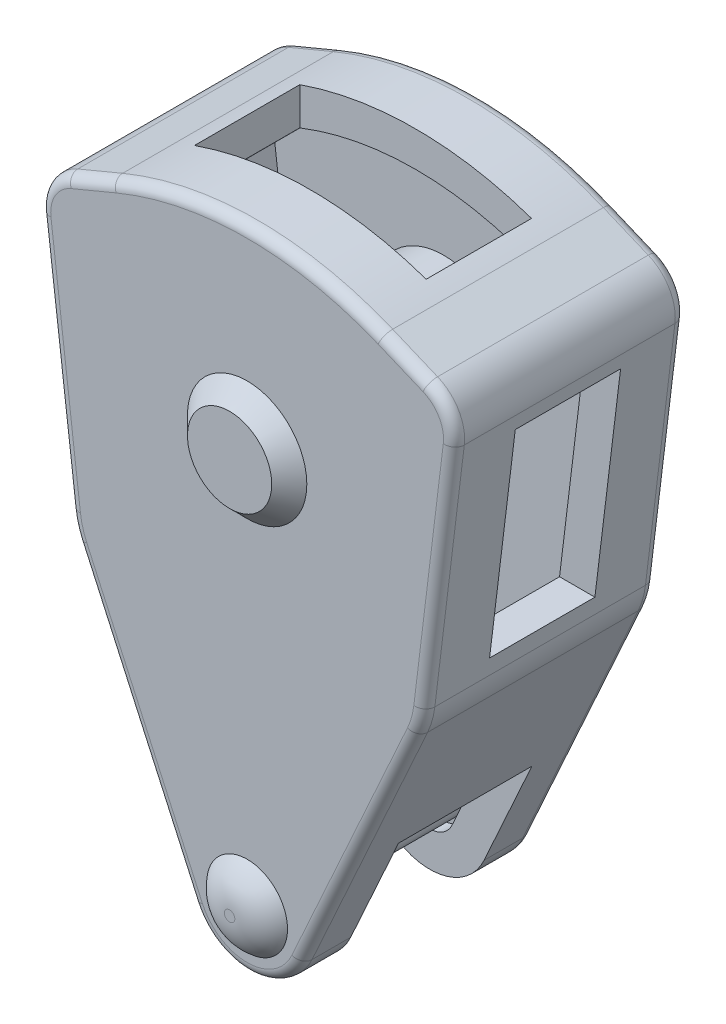
SolidWorks part; units mm, degrees
material "ABS"
ref_plane "Front Plane" through (0, 0, 0) normal (0, 0, 1) x (1, 0, 0)
ref_plane "Top Plane" through (0, 0, 0) normal (0, 1, 0) x (1, 0, 0)
ref_plane "Right Plane" through (0, 0, 0) normal (1, 0, 0) x (0, 0, -1)
sketch "Sketch1" plane through (0, 0, 0) normal (0, 0, 1) x (1, 0, 0)
  line L0 (3.9317, -1.7852) -> (12.7, 17.526)
  line L1 (12.7, 17.526) -> (15.24, 38.354)
  line L2 (15.24, 38.354) -> (0, 44.704)
  line L3 (0, 0) -> (0, 44.704) construction
  line L4 (0, 0) -> (0, -4.318) construction
  line L5 (-15.24, 38.354) -> (0, 44.704)
  line L6 (-12.7, 17.526) -> (-15.24, 38.354)
  line L7 (-3.9317, -1.7852) -> (-12.7, 17.526)
  arc A0 (-3.9317, -1.7852) -> (3.9317, -1.7852) centre (0, 0) ccw
  dimension "D1" = 8.636
  dimension "D2" = 12.7
  dimension "D3" = 15.24
  dimension "D4" = 49.022
  dimension "D5" = 21.844
  dimension "D6" = 42.672
extrude "Boss-Extrude1" add sketch "Sketch1" along normal mid plane 16.764
fillet "Fillet1" radius 25.4 1 edges at (0, 44.704, 0)
fillet "Fillet2" radius 3.175 2 edges at (15.24, 38.354, 0) (-15.24, 38.354, 0)
fillet "Fillet3" radius 6.35 2 edges at (12.7, 17.526, 0) (-12.7, 17.526, 0)
shell "Shell1" thickness 2.54
sketch "Sketch2" plane through (0, 0, 0) normal (1, 0, 0) x (0, 0, -1)
  line L0 (-8.382, -4.318) -> (8.382, -4.318) construction
  line L1 (-4.826, -4.318) -> (4.826, -4.318)
  line L2 (-4.826, -4.318) -> (-4.826, 5.842)
  line L3 (-4.826, 5.842) -> (4.826, 5.842)
  line L4 (4.826, -4.318) -> (4.826, 5.842)
  line L5 (0, 5.842) -> (0, 0) construction
  dimension "D1" = 9.652
  dimension "D2" = 10.16
extrude "Cut-Extrude1" cut sketch "Sketch2" against normal through all and the other way through all
sketch "Sketch3" plane through (0, 0, 8.382) normal (0, 0, 1) x (1, 0, 0)
  circle A0 centre (0, 0) radius 1.397
  dimension "D1" = 2.794
extrude "Boss-Extrude2" add sketch "Sketch3" against normal up to surface (16.764 mm away) up to face at (0, 24.8733, -8.382)
sketch "Sketch4" plane through (0, 0, 8.382) normal (0, 0, 1) x (1, 0, 0)
  circle A0 centre (0, 0) radius 2.921
  dimension "D1" = 5.842
extrude "Boss-Extrude3" add sketch "Sketch4" along normal blind 1.27
mirror "Mirror1" about plane through (0, 0, 0) normal (0, 0, 1) of "Boss-Extrude3"
fillet "Fillet4" radius 3.175 2 edges at (2.921, 0, -9.652) (2.921, 0, 9.652)
sketch "Sketch5" plane through (0, 0, 0) normal (1, 0, 0) x (0, 0, -1)
  line L0 (8.382, 42.5873) -> (-8.382, 42.5873) construction
  line L1 (-3.81, 19.7273) -> (3.81, 19.7273)
  line L2 (-3.81, 19.7273) -> (-3.81, 34.9673)
  line L3 (-3.81, 34.9673) -> (3.81, 34.9673)
  line L4 (3.81, 19.7273) -> (3.81, 34.9673)
  line L5 (-3.81, 19.7273) -> (3.81, 34.9673) construction
  line L6 (-3.81, 34.9673) -> (3.81, 19.7273) construction
  point P0 (0, 27.3473)
  dimension "D1" = 7.62
  dimension "D2" = 15.24
  dimension "D3" = 7.62
extrude "Cut-Extrude2" cut sketch "Sketch5" against normal through all both and the other way through all
sketch "Sketch6" plane through (0, 0, 8.382) normal (0, 0, 1) x (1, 0, 0)
  circle A0 centre (0, 28.575) radius 5.08
  dimension "D1" = 10.16
  dimension "D2" = 28.575
extrude "Boss-Extrude4" add sketch "Sketch6" against normal up to surface (16.764 mm away) up to face at (2.921, 0, -8.382)
sketch "Sketch7" plane through (0, 0, 8.382) normal (0, 0, 1) x (1, 0, 0)
  circle A0 centre (0, 28.575) radius 4.318
  dimension "D1" = 8.636
extrude "Boss-Extrude5" add sketch "Sketch7" along normal blind 1.27
mirror "Mirror2" about plane through (0, 0, 0) normal (0, 0, 1) of "Boss-Extrude5"
chamfer "Chamfer1" distance 1.27 angle 45 2 edges at (4.318, 28.575, -9.652) (4.318, 28.575, 9.652)
sketch "Sketch9" plane through (0, 0, 0) normal (0, 0, 1) x (1, 0, 0)
  line L0 (12.0412, 36.9352) -> (8.7923, 38.2889) construction
  line L1 (-8.382, 51.1598) -> (8.382, 51.1598)
  line L2 (-8.382, 51.1598) -> (-8.382, 38.4598)
  line L3 (-8.382, 38.4598) -> (8.382, 38.4598)
  line L4 (8.382, 51.1598) -> (8.382, 38.4598)
  line L5 (-8.382, 51.1598) -> (8.382, 38.4598) construction
  line L6 (-8.382, 38.4598) -> (8.382, 51.1598) construction
  point P0 (0, 44.8098)
  dimension "D1" = 16.764
  dimension "D2" = 12.7
extrude "Cut-Extrude3" cut sketch "Sketch9" against normal mid plane 7.62
fillet "Fillet5" radius 0.762 24 edges at (0, -4.318, -8.382) (-8.1142, 7.4263, -8.382) (-12.6283, 17.5461, -8.382) (-13.8834, 27.2295, -8.382) (-14.5407, 37.9468, -8.382) (-11.3937, 39.9566, -8.382) (0, 42.5873, -8.382) (11.3937, 39.9566, -8.382) (14.5407, 37.9468, -8.382) (13.8834, 27.2295, -8.382) (12.6283, 17.5461, -8.382) (12.6283, 17.5461, 8.382) (8.1142, 7.4263, 8.382) (0, -4.318, 8.382) (-8.1142, 7.4263, 8.382) (-12.6283, 17.5461, 8.382) (-13.8834, 27.2295, 8.382) (-14.5407, 37.9468, 8.382) (-11.3937, 39.9566, 8.382) (0, 42.5873, 8.382) (11.3937, 39.9566, 8.382) (14.5407, 37.9468, 8.382) (8.1142, 7.4263, -8.382) (13.8834, 27.2295, 8.382)
